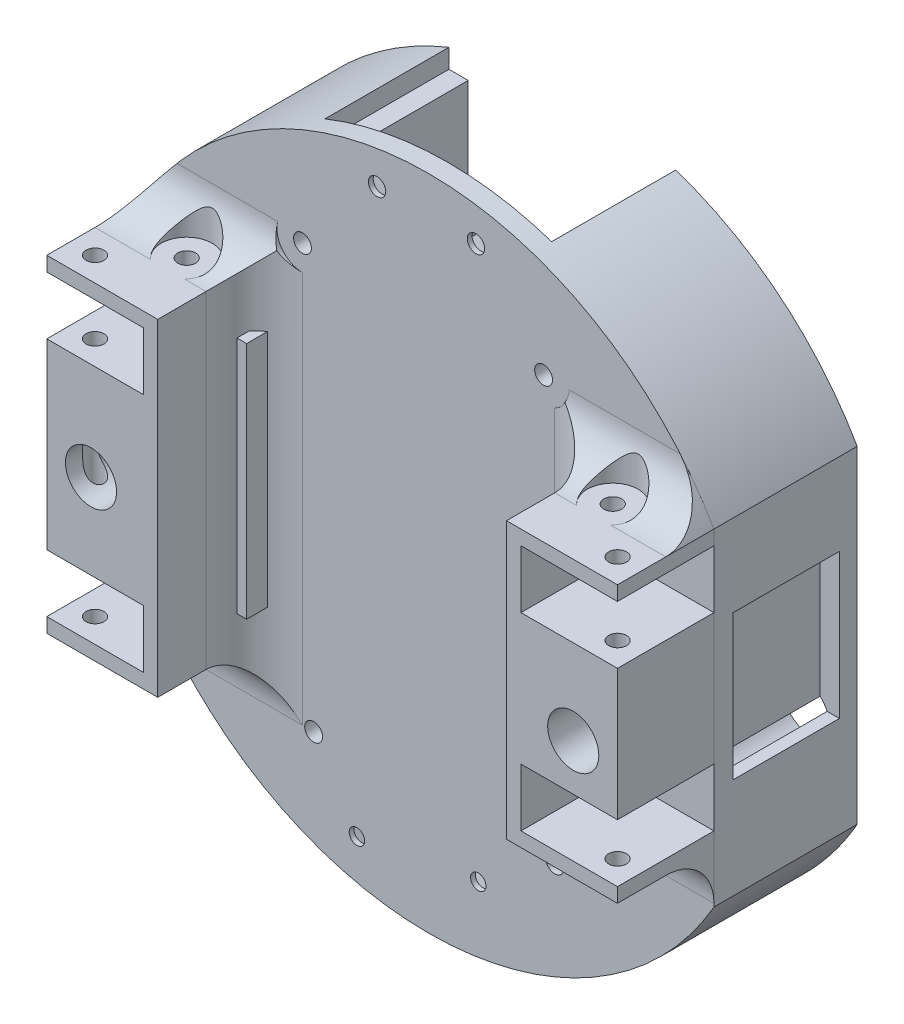
SolidWorks part; units mm, degrees
ref_plane "Alzado" through (0, 0, 0) normal (0, 0, 1) x (1, 0, 0)
ref_plane "Planta" through (0, 0, 0) normal (0, 1, 0) x (1, 0, 0)
ref_plane "Vista lateral" through (0, 0, 0) normal (1, 0, 0) x (0, 0, -1)
sketch "Croquis1" plane through (0, 0, 0) normal (0, 0, 1) x (1, 0, 0)
  line L0 (-13.4238, -120.2944) -> (-13.4238, -132.2944) construction
  line L1 (-13.4238, -132.2944) -> (-9.4238, -132.2944) construction
  line L2 (-9.4238, -132.2944) -> (-9.4238, -256.2944) construction
  line L3 (-9.4238, -256.2944) -> (33.5762, -256.2944) construction
  line L4 (33.5762, -120.2944) -> (33.5762, -256.2944) construction
  line L5 (-13.4238, -120.2944) -> (-13.4238, -132.2944)
  line L6 (-13.4238, -132.2944) -> (-9.4238, -132.2944)
  line L7 (-9.4238, -132.2944) -> (-9.4238, -256.2944)
  line L8 (-9.4238, -256.2944) -> (33.5762, -256.2944)
  line L9 (33.5762, -120.2944) -> (33.5762, -256.2944)
  circle A2 centre (12.066, -191.5898) radius 68.188
  circle A3 centre (12.066, -191.5898) radius 43.8976
extrude "Saliente-Extruir2" add sketch "Croquis1" along normal blind 25.7 contours A3 L7 L6 L5 A2 L9 L8 region at (-15.328, -130.3199, 0)
sketch "Croquis3" plane through (0, 0, 25.7) normal (0, 0, 1) x (1, 0, 0)
  circle A0 centre (12.066, -191.5898) radius 68.188
extrude "Saliente-Extruir3" add sketch "Croquis3" along normal blind 4
sketch "Croquis6" plane through (0, 0, 29.7) normal (0, 0, 1) x (1, 0, 0)
  line L0 (-47.0808, -157.6597) -> (-47.0808, -225.5199)
  line L1 (71.2129, -157.6597) -> (71.2129, -225.5199)
  circle A0 centre (12.066, -191.5898) radius 68.188 construction
  circle A1 centre (12.066, -191.5898) radius 68.188
  circle M2 centre (12.066, -191.5898) radius 68.188
extrude "Cortar-Extruir1" cut sketch "Croquis6" against normal up to surface (29.7 mm away) contours L0 M2 | L1 M2 region at (-50.7186, -191.5898, 29.7) region at (74.8507, -191.5898, 29.7)
sketch "Croquis7" plane through (-47.0808, 0, 0) normal (-1, 0, 0) x (0, 0, 1)
  line L0 (0, -157.6597) -> (29.7, -157.6597) construction
  line L1 (27.7, -164.6597) -> (2.7, -164.6597)
  line L2 (27.7, -164.6597) -> (27.7, -219.1597)
  line L3 (27.7, -219.1597) -> (2.7, -219.1597)
  line L4 (2.7, -164.6597) -> (2.7, -219.1597)
  line L5 (27.7, -164.6597) -> (2.7, -219.1597) construction
  line L6 (27.7, -219.1597) -> (2.7, -164.6597) construction
  line L7 (29.7, -157.6597) -> (29.7, -225.5199) construction
  point P0 (15.2, -191.9097)
  dimension "D1" = 54.5
  dimension "D2" = 25
  dimension "D3" = 7
  dimension "D4" = 2
extrude "Cortar-Extruir2" cut sketch "Croquis7" against normal blind 2
sketch "Croquis8" plane through (-45.0808, 0, 0) normal (-1, 0, 0) x (0, 0, 1)
  line L0 (2.7, -219.1597) -> (27.7, -219.1597) construction
  line L3 (2.7, -164.6597) -> (2.7, -219.1597) construction
  line L4 (27.7, -219.1597) -> (27.7, -164.6597) construction
  line L7 (27.7, -164.6597) -> (2.7, -164.6597) construction
  circle A0 centre (5.7, -209.1597) radius 1.6
  circle A1 centre (24.7, -174.9597) radius 1.6
  dimension "D1" = 3.2
  dimension "D2" = 3.2
  dimension "D3" = 10
  dimension "D4" = 3
  dimension "D5" = 3
  dimension "D6" = 10.3
extrude "Cortar-Extruir3" cut sketch "Croquis8" against normal blind 10
sketch "Croquis9" plane through (71.2129, 0, 0) normal (1, 0, 0) x (0, 0, -1)
  line L0 (-29.7, -157.6597) -> (-29.7, -225.5199) construction
  line L1 (-25.7, -204.6597) -> (-3.7, -204.6597)
  line L2 (-25.7, -204.6597) -> (-25.7, -174.6597)
  line L3 (-25.7, -174.6597) -> (-3.7, -174.6597)
  line L4 (-3.7, -204.6597) -> (-3.7, -174.6597)
  line L5 (-25.7, -204.6597) -> (-3.7, -174.6597) construction
  line L6 (-25.7, -174.6597) -> (-3.7, -204.6597) construction
  line L7 (0, -157.6597) -> (-29.7, -157.6597) construction
  point P0 (-14.7, -189.6597)
  dimension "D1" = 30
  dimension "D2" = 22
  dimension "D3" = 4
  dimension "D4" = 17
extrude "Cortar-Extruir4" cut sketch "Croquis9" against normal blind 4
sketch "Croquis10" plane through (0, 0, 0) normal (0, 0, -1) x (-1, 0, 0)
  circle A0 centre (11.7683, -235.5435) radius 1.85
  circle A1 centre (-38.2139, -234.2077) radius 1.85
  circle A2 centre (37.9161, -192.9255) radius 1.85
  circle A3 centre (-62.0482, -190.2541) radius 1.85
  circle A4 centre (-35.9003, -147.6361) radius 1.85
  circle A5 centre (14.0818, -148.9719) radius 1.85
extrude "Cortar-Extruir5" cut sketch "Croquis10" against normal through all
sketch "Croquis11" plane through (0, 0, 29.7) normal (0, 0, 1) x (1, 0, 0)
  line L1 (-6.6149, -135.8646) -> (29.8796, -135.8646)
  line L2 (-6.6149, -135.8646) -> (-6.6149, -150.703)
  line L3 (-6.6149, -150.703) -> (29.8796, -150.703)
  line L4 (29.8796, -135.8646) -> (29.8796, -150.703)
extrude "Saliente-Extruir4" add sketch "Croquis11" along normal up to surface (5 mm away)
sketch "Croquis12" plane through (0, 0, 34.7) normal (0, 0, 1) x (1, 0, 0)
  line L0 (-6.6149, -135.8646) -> (-6.6149, -150.703) construction
  line L1 (-6.6149, -143.2838) -> (29.8796, -143.2838)
  line L2 (-6.6149, -143.2838) -> (-6.6149, -135.8646)
  line L3 (-6.6149, -135.8646) -> (29.8796, -135.8646)
  line L4 (29.8796, -143.2838) -> (29.8796, -135.8646)
extrude "Saliente-Extruir5" add sketch "Croquis12" along normal blind 60
sketch "Croquis13" plane through (29.8796, 0, 0) normal (1, 0, 0) x (0, 0, -1)
  line L0 (-94.7, -143.2838) -> (-34.7, -143.2838) construction
  line L1 (-67.8927, -143.2838) -> (-65.6955, -143.2838)
  line L2 (-67.8927, -143.2838) -> (-67.8927, -140.5858)
  line L3 (-67.8927, -140.5858) -> (-65.6955, -140.5858)
  line L4 (-65.6955, -143.2838) -> (-65.6955, -140.5858)
extrude "Cortar-Extruir6" cut sketch "Croquis13" against normal through all
sketch "Croquis15" plane through (0, 0, 29.7) normal (0, 0, 1) x (1, 0, 0)
  line L0 (-19.658, -153.6519) -> (-19.658, -207.8491) construction
  line L1 (-19.658, -166.7959) -> (-21.658, -166.7959)
  line L2 (-19.658, -166.7959) -> (-19.658, -216.285)
  line L3 (-19.658, -216.285) -> (-21.658, -216.285)
  line L4 (-21.658, -166.7959) -> (-21.658, -216.285)
  line L5 (42.342, -153.6519) -> (42.342, -232.8491) construction
  line L6 (42.342, -166.7959) -> (44.342, -166.7959)
  line L7 (42.342, -166.7959) -> (42.342, -216.285)
  line L8 (42.342, -216.285) -> (44.342, -216.285)
  line L9 (44.342, -166.7959) -> (44.342, -216.285)
  dimension "D1" = 2
  dimension "D2" = 2
extrude "Saliente-Extruir6" add sketch "Croquis15" along normal blind 6
sketch "Croquis16" plane through (0, 0, 29.7) normal (0, 0, 1) x (1, 0, 0)
  circle A0 centre (-2.7952, -249.8624) radius 1.6
  circle A1 centre (22.3692, -245.4021) radius 1.6
  dimension "D1" = 3.2
  dimension "D2" = 3.2
extrude "Cortar-Extruir7" cut sketch "Croquis16" against normal blind 10
sketch "Croquis17" plane through (0, -143.2838, 0) normal (0, -1, 0) x (-1, 0, 0)
  circle A0 centre (0.578, -88.2) radius 1.85
  circle A1 centre (-10.0711, -88.2) radius 1.85
  circle A2 centre (-21.422, -88.2) radius 1.85
  dimension "D1" = 3.7
  dimension "D2" = 3.7
  dimension "D3" = 3.7
extrude "Cortar-Extruir8" cut sketch "Croquis17" against normal through all
sketch "Croquis23" plane through (0, 0, 29.7) normal (0, 0, 1) x (1, 0, 0)
  line L0 (-21.658, -166.7959) -> (-21.658, -216.285) construction
  line L1 (-47.0808, -157.6597) -> (-21.658, -157.6597)
  line L2 (-47.0808, -157.6597) -> (-47.0808, -175.6597)
  line L3 (-47.0808, -175.6597) -> (-21.658, -175.6597)
  line L4 (-21.658, -157.6597) -> (-21.658, -175.6597)
  line L5 (44.342, -216.285) -> (44.342, -166.7959) construction
  line L6 (-47.0808, -225.5199) -> (-21.658, -225.5199)
  line L7 (-47.0808, -225.5199) -> (-47.0808, -207.5199)
  line L8 (-47.0808, -207.5199) -> (-21.658, -207.5199)
  line L9 (-21.658, -225.5199) -> (-21.658, -207.5199)
  line L10 (71.2129, -157.6597) -> (44.342, -157.6597)
  line L11 (71.2129, -157.6597) -> (71.2129, -175.6597)
  line L12 (71.2129, -175.6597) -> (44.342, -175.6597)
  line L13 (44.342, -157.6597) -> (44.342, -175.6597)
  line L14 (71.2129, -157.6597) -> (71.2129, -225.5199) construction
  line L15 (71.2129, -214.8491) -> (44.342, -214.8491)
  line L16 (71.2129, -214.8491) -> (71.2129, -196.8491)
  line L17 (71.2129, -196.8491) -> (44.342, -196.8491)
  line L18 (44.342, -214.8491) -> (44.342, -196.8491)
  dimension "D1" = 18
  dimension "D2" = 18
  dimension "D3" = 18
  dimension "D4" = 18
extrude "Saliente-Extruir8" add sketch "Croquis23" along normal blind 20
sketch "Croquis24" plane through (0, 0, 49.7) normal (0, 0, 1) x (1, 0, 0)
  line L0 (-47.0808, -157.6597) -> (-47.0808, -175.6597) construction
  line L1 (-47.0808, -172.6597) -> (-27.0808, -172.6597)
  line L2 (-47.0808, -172.6597) -> (-47.0808, -160.6597)
  line L3 (-47.0808, -160.6597) -> (-27.0808, -160.6597)
  line L4 (-27.0808, -172.6597) -> (-27.0808, -160.6597)
  line L5 (-47.0808, -207.5199) -> (-47.0808, -225.5199) construction
  line L6 (-47.0808, -222.5199) -> (-27.0808, -222.5199)
  line L7 (-47.0808, -222.5199) -> (-47.0808, -210.5199)
  line L8 (-47.0808, -210.5199) -> (-27.0808, -210.5199)
  line L9 (-27.0808, -222.5199) -> (-27.0808, -210.5199)
  line L10 (71.2129, -175.6597) -> (71.2129, -157.6597) construction
  line L11 (71.2129, -160.6597) -> (51.2129, -160.6597)
  line L12 (71.2129, -160.6597) -> (71.2129, -172.6597)
  line L13 (71.2129, -172.6597) -> (51.2129, -172.6597)
  line L14 (51.2129, -160.6597) -> (51.2129, -172.6597)
  line L15 (71.2129, -214.8491) -> (71.2129, -196.8491) construction
  line L16 (71.2129, -199.8491) -> (51.2129, -199.8491)
  line L17 (71.2129, -199.8491) -> (71.2129, -211.8491)
  line L18 (71.2129, -211.8491) -> (51.2129, -211.8491)
  line L19 (51.2129, -199.8491) -> (51.2129, -211.8491)
  line L20 (-21.658, -157.6597) -> (-47.0808, -157.6597) construction
  line L21 (-47.0808, -225.5199) -> (-21.658, -225.5199) construction
  line L22 (71.2129, -157.6597) -> (44.342, -157.6597) construction
  line L23 (71.2129, -196.8491) -> (44.342, -196.8491) construction
  line L24 (-47.0808, -175.6597) -> (-21.658, -175.6597) construction
  line L25 (-21.658, -157.6597) -> (-24.0808, -157.6597)
  line L26 (-21.658, -157.6597) -> (-21.658, -175.6597)
  line L27 (-21.658, -175.6597) -> (-24.0808, -175.6597)
  line L28 (-24.0808, -157.6597) -> (-24.0808, -175.6597)
  line L29 (-47.0808, -225.5199) -> (-21.658, -225.5199) construction
  line L30 (-21.658, -207.5199) -> (-24.0808, -207.5199)
  line L31 (-21.658, -207.5199) -> (-21.658, -225.5199)
  line L32 (-21.658, -225.5199) -> (-24.0808, -225.5199)
  line L33 (-24.0808, -207.5199) -> (-24.0808, -225.5199)
  line L34 (44.342, -175.6597) -> (71.2129, -175.6597) construction
  line L35 (44.342, -157.6597) -> (48.2129, -157.6597)
  line L36 (44.342, -157.6597) -> (44.342, -175.6597)
  line L37 (44.342, -175.6597) -> (48.2129, -175.6597)
  line L38 (48.2129, -157.6597) -> (48.2129, -175.6597)
  line L39 (44.342, -214.8491) -> (71.2129, -214.8491) construction
  line L40 (44.342, -196.8491) -> (48.2129, -196.8491)
  line L41 (44.342, -196.8491) -> (44.342, -214.8491)
  line L42 (44.342, -214.8491) -> (48.2129, -214.8491)
  line L43 (48.2129, -196.8491) -> (48.2129, -214.8491)
  dimension "D1" = 12
  dimension "D2" = 12
  dimension "D3" = 12
  dimension "D4" = 12
  dimension "D5" = 3
  dimension "D6" = 3
  dimension "D7" = 3
  dimension "D8" = 3
  dimension "D9" = 20
  dimension "D10" = 20
  dimension "D11" = 20
  dimension "D12" = 20
  dimension "D13" = 3
  dimension "D14" = 3
  dimension "D15" = 3
  dimension "D16" = 3
extrude "Cortar-Extruir12" cut sketch "Croquis24" against normal blind 20
sketch "Croquis25" plane through (0, -157.6597, 0) normal (0, 1, 0) x (1, 0, 0)
  line L0 (-47.0808, -49.7) -> (-47.0808, -29.7) construction
  line L2 (-24.0808, -49.7) -> (-47.0808, -49.7) construction
  line L3 (-24.0808, -29.7) -> (-24.0808, -49.7) construction
  line L4 (-24.0808, -29.7) -> (-47.0808, -29.7) construction
  line L5 (12.0762, -94.7) -> (12.0762, 4.7088) construction
  line L6 (29.8796, -94.7) -> (-6.6149, -94.7) construction
  circle A0 centre (-42.0808, -44.7) radius 1.85
  circle A1 centre (-32.0808, -35.7) radius 1.85
  circle A2 centre (66.2332, -44.7) radius 1.85
  circle A3 centre (56.2332, -35.7) radius 1.85
  dimension "D1" = 3.7
  dimension "D2" = 3.7
  dimension "D3" = 5
  dimension "D4" = 5
  dimension "D5" = 8
  dimension "D6" = 6
extrude "Cortar-Extruir13" cut sketch "Croquis25" against normal through all
sketch "Croquis26" plane through (0, 0, 0) normal (0, 0, -1) x (-1, 0, 0)
  line L0 (-12.066, -191.5898) -> (-12.066, -114.417) construction
  circle A1 centre (34.6799, -216.4704) radius 7
  circle A2 centre (34.6799, -167.6419) radius 7
  circle A5 centre (-58.812, -167.6419) radius 7
  circle A6 centre (-62.4, -207.7488) radius 7
  dimension "D2" = 14
  dimension "D3" = 14
extrude "Cortar-Extruir14" cut sketch "Croquis26" against normal blind 23
sketch "Croquis27" plane through (0, 0, 25.7) normal (0, 0, -1) x (-1, 0, 0)
  line L1 (-25.7146, -247.8694) -> (-21.9051, -249.533)
  line L2 (-21.9051, -249.533) -> (-18.5596, -247.0657)
  line L3 (-18.5596, -247.0657) -> (-19.0237, -242.9347)
  line L4 (-19.0237, -242.9347) -> (-22.8332, -241.2711)
  line L5 (-22.8332, -241.2711) -> (-26.1787, -243.7385)
  line L6 (-26.1787, -243.7385) -> (-25.7146, -247.8694)
  line L7 (0.3215, -253.2032) -> (4.4516, -253.6751)
  line L8 (4.4516, -253.6751) -> (6.9252, -250.3343)
  line L9 (6.9252, -250.3343) -> (5.2688, -246.5216)
  line L10 (5.2688, -246.5216) -> (1.1388, -246.0498)
  line L11 (1.1388, -246.0498) -> (-1.3349, -249.3906)
  line L12 (-1.3349, -249.3906) -> (0.3215, -253.2032)
  circle A0 centre (-22.3692, -245.4021) radius 3.6 construction
  circle A1 centre (2.7952, -249.8624) radius 3.6 construction
  dimension "D1" = 7.2
  dimension "D2" = 7.2
extrude "Cortar-Extruir15" cut sketch "Croquis27" against normal blind 3
sketch "Croquis28" plane through (0, -135.8646, 0) normal (0, 1, 0) x (1, 0, 0)
  line L0 (29.8796, -94.7) -> (29.8796, -29.7) construction
  line L1 (3.8796, -74.2) -> (18.8796, -74.2)
  line L2 (3.8796, -74.2) -> (3.8796, -83.2)
  line L3 (3.8796, -83.2) -> (18.8796, -83.2)
  line L4 (18.8796, -74.2) -> (18.8796, -83.2)
  line L5 (3.8796, -74.2) -> (18.8796, -83.2) construction
  line L6 (3.8796, -83.2) -> (18.8796, -74.2) construction
  line L7 (29.8796, -94.7) -> (-6.6149, -94.7) construction
  line L9 (3.8796, -47.7) -> (21.8796, -47.7)
  line L10 (3.8796, -47.7) -> (3.8796, -63.7)
  line L11 (3.8796, -63.7) -> (21.8796, -63.7)
  line L12 (21.8796, -47.7) -> (21.8796, -63.7)
  line L13 (3.8796, -47.7) -> (21.8796, -63.7) construction
  line L14 (3.8796, -63.7) -> (21.8796, -47.7) construction
  point P0 (11.3796, -78.7)
  point P9 (12.8796, -55.7)
  dimension "D1" = 15
  dimension "D2" = 9
  dimension "D3" = 11
  dimension "D4" = 16
  dimension "D5" = 18
  dimension "D6" = 16
  dimension "D7" = 8
  dimension "D8" = 31
extrude "Cortar-Extruir16" cut sketch "Croquis28" against normal blind 10
sketch "Croquis29" plane through (0, -135.8646, 0) normal (0, 1, 0) x (1, 0, 0)
  circle A0 centre (10.0711, -88.2) radius 1.85
extrude "Saliente-Extruir9" add sketch "Croquis29" against normal up to surface (7.4192 mm away) up to face at (11.3796, -143.2838, 78.7)
sketch "Croquis30" plane through (0, 0, 29.7) normal (0, 0, 1) x (1, 0, 0)
  line L0 (48.2129, -175.6597) -> (71.2129, -175.6597) construction
  line L1 (-47.0808, -175.6597) -> (-24.0808, -175.6597)
  line L2 (-47.0808, -175.6597) -> (-47.0808, -207.5199)
  line L3 (-47.0808, -207.5199) -> (-24.0808, -207.5199)
  line L4 (-24.0808, -175.6597) -> (-24.0808, -207.5199)
  line L5 (48.2129, -175.6597) -> (71.2129, -175.6597)
  line L6 (48.2129, -175.6597) -> (48.2129, -196.8491)
  line L7 (48.2129, -196.8491) -> (71.2129, -196.8491)
  line L8 (71.2129, -175.6597) -> (71.2129, -196.8491)
  line L9 (71.2129, -175.6597) -> (71.2129, -196.8491) construction
  line L10 (71.2129, -196.8491) -> (48.2129, -196.8491) construction
  circle A0 centre (-37.9161, -192.9255) radius 5.3
  circle A1 centre (62.0482, -190.2541) radius 5.3
  dimension "D1" = 10.6
  dimension "D2" = 10.6
extrude "Saliente-Extruir10" add sketch "Croquis30" along normal up to surface (20 mm away) up to face at (-36.3308, -166.6597, 49.7)
sketch "Croquis31" plane through (0, -225.5199, 0) normal (0, -1, 0) x (1, 0, 0)
  circle A0 centre (-42.0808, 44.7) radius 1.85
  circle A1 centre (-32.0808, 35.7) radius 1.85
  circle A2 centre (56.2332, 35.7) radius 1.85
  circle A3 centre (66.2332, 44.7) radius 1.85
extrude "Cortar-Extruir17" cut sketch "Croquis31" against normal through all
fillet "Redondeo2" radius 10 6 edges at (59.7129, -157.6597, 29.7) (-35.5808, -157.6597, 29.7) (48.2129, -186.2544, 29.7) (-24.0808, -191.5898, 29.7) (59.7129, -214.8491, 29.7) (-35.5808, -225.5199, 29.7)
sketch "Croquis32" plane through (0, 0, 29.7) normal (0, 0, 1) x (1, 0, 0)
  circle A0 centre (-14.0818, -148.9719) radius 5.3
  circle A1 centre (35.9003, -147.6361) radius 5.3
  dimension "D1" = 10.6
  dimension "D2" = 10.6
extrude "Cortar-Extruir18" cut sketch "Croquis32" along normal through all
sketch "Croquis33" plane through (0, -225.5199, 0) normal (0, -1, 0) x (1, 0, 0)
  circle A0 centre (-32.0808, 35.7) radius 5.3
  circle A1 centre (56.2332, 35.7) radius 5.3
  dimension "D1" = 10.6
  dimension "D2" = 10.6
extrude "Cortar-Extruir19" cut sketch "Croquis33" along normal blind 10
sketch "Croquis35" plane through (0, -157.6597, 0) normal (0, 1, 0) x (1, 0, 0)
  circle A0 centre (-32.0808, -35.7) radius 5.3
  circle A1 centre (56.2332, -35.7) radius 5.3
  dimension "D1" = 10.6
  dimension "D2" = 10.6
extrude "Cortar-Extruir21" cut sketch "Croquis35" along normal blind 10
sketch "Croquis37" plane through (0, -214.8491, 0) normal (0, -1, 0) x (1, 0, 0)
  circle A0 centre (56.2332, 35.7) radius 5.3
  dimension "D1" = 10.6
extrude "Cortar-Extruir23" cut sketch "Croquis37" along normal blind 10
sketch "Croquis38" plane through (-6.6149, 0, 0) normal (-1, 0, 0) x (0, 0, 1)
  line L0 (94.7, -135.8646) -> (29.7, -135.8646) construction
  line L1 (34.6572, -135.8646) -> (29.7026, -135.8646)
  line L2 (34.6572, -135.8646) -> (34.6572, -126.3384)
  line L3 (34.6572, -126.3384) -> (29.7026, -126.3384)
  line L4 (29.7026, -135.8646) -> (29.7026, -126.3384)
  point P7 (34.6572, -125.2854)
  point P8 (29.7026, -126.3384)
extrude "Saliente-Extruir11" add sketch "Croquis38" against normal up to surface (36.4945 mm away) up to face at (29.8796, -142.7442, 58.5376)
sketch "Croquis39" plane through (0, 0, 34.6572) normal (0, 0, 1) x (1, 0, 0)
  line L0 (-6.6149, -131.1015) -> (29.8796, -131.1015) construction
  line L1 (-6.6149, -135.8646) -> (-6.6149, -126.3384) construction
  line L2 (29.8796, -126.3384) -> (29.8796, -135.8646) construction
  circle A0 centre (1.3851, -131.1015) radius 1.8
  circle A1 centre (21.8796, -131.1015) radius 1.8
  dimension "D1" = 3.6
  dimension "D2" = 3.6
  dimension "D3" = 8
  dimension "D4" = 8
extrude "Cortar-Extruir24" cut sketch "Croquis39" against normal through all
sketch "Croquis40" plane through (0, 0, 25.7) normal (0, 0, -1) x (-1, 0, 0)
  line L1 (-18.5232, -132.7802) -> (-18.7476, -129.0341)
  line L2 (-18.7476, -129.0341) -> (-22.1041, -127.3555)
  line L3 (-22.1041, -127.3555) -> (-25.236, -129.4229)
  line L4 (-25.236, -129.4229) -> (-25.0115, -133.169)
  line L5 (-25.0115, -133.169) -> (-21.6551, -134.8476)
  line L6 (-21.6551, -134.8476) -> (-18.5232, -132.7802)
  line L7 (-0.4642, -134.7396) -> (2.226, -132.123)
  line L8 (2.226, -132.123) -> (1.305, -128.485)
  line L9 (1.305, -128.485) -> (-2.3061, -127.4635)
  line L10 (-2.3061, -127.4635) -> (-4.9962, -130.0801)
  line L11 (-4.9962, -130.0801) -> (-4.0753, -133.7181)
  line L12 (-4.0753, -133.7181) -> (-0.4642, -134.7396)
  circle A0 centre (-21.8796, -131.1015) radius 3.25 construction
  circle A1 centre (-1.3851, -131.1015) radius 3.25 construction
  dimension "D1" = 6.5
  dimension "D2" = 6.5
extrude "Cortar-Extruir25" cut sketch "Croquis40" against normal blind 3
ref_plane "Plano1" through (0, 0, 29.7) normal (0, 0, 1) x (1, 0, 0)
split "Partir1" trim tools "Plano1" bodies to split 139 resulting bodies 140 141 142 143
sketch "Croquis45" plane through (0, 0, 29.7) normal (0, 0, 1) x (1, 0, 0)
  line L0 (29.8796, -150.703) -> (29.8796, -143.2838) construction
  line L1 (-6.6149, -126.3384) -> (29.8796, -126.3384)
  line L2 (-6.6149, -126.3384) -> (-6.6149, -150.703)
  line L3 (-6.6149, -150.703) -> (29.8796, -150.703)
  line L4 (29.8796, -126.3384) -> (29.8796, -150.703)
extrude "Cortar-Extruir26" cut sketch "Croquis45" along normal through all
